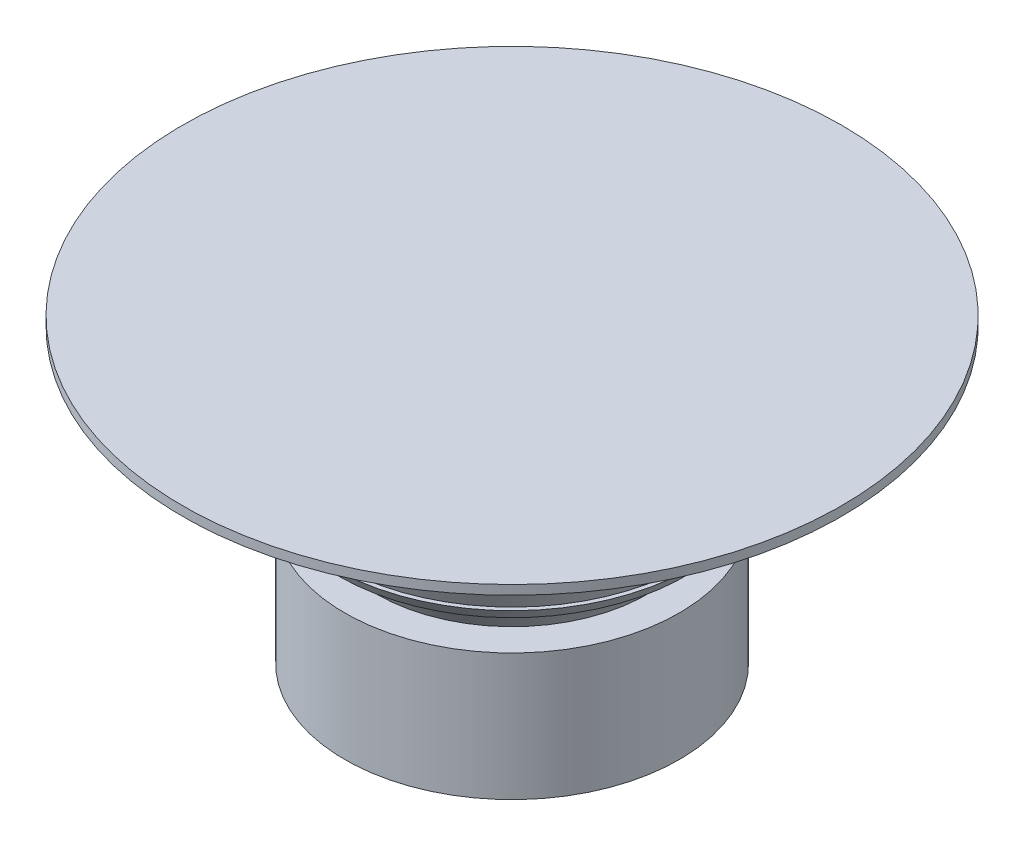
SolidWorks part; units mm, degrees
ref_plane "Front Plane" through (0, 0, 0) normal (0, 0, 1) x (1, 0, 0)
ref_plane "Top Plane" through (0, 0, 0) normal (0, 1, 0) x (1, 0, 0)
ref_plane "Right Plane" through (0, 0, 0) normal (1, 0, 0) x (0, 0, -1)
sketch "Sketch1" plane through (0, 0, 0) normal (0, 0, 1) x (1, 0, 0)
  line L0 (0, 123.363) -> (-135.2932, 123.363)
  line L1 (-135.2932, 119.5555) -> (-113.7173, 119.5555)
  line L2 (-113.7173, 119.5555) -> (-113.7173, 111.9405)
  line L3 (0, 109.9098) -> (-45.4362, 109.9098)
  line L4 (0, 70.8195) -> (-17.0068, 70.8195)
  line L5 (-17.5145, 66.2505) -> (-40.8672, 66.2505)
  line L6 (-71.8348, 67.2658) -> (-74.1193, 70.8195)
  line L7 (-64.7275, 66.2505) -> (-70.058, 66.2505)
  line L8 (-55.5895, 52.0358) -> (-63.2045, 65.2352)
  line L9 (0, 119.5555) -> (-113.7173, 119.5555)
  line L10 (-82.242, 97.472) -> (-72.0887, 70.8195)
  line L11 (-80.2113, 92.3953) -> (-81.7343, 95.949)
  line L12 (-81.7343, 95.949) -> (-83.2573, 99.5027)
  line L13 (-83.2573, 99.5027) -> (-84.7803, 103.0563)
  line L14 (-84.7803, 103.0563) -> (-86.5572, 106.61)
  line L15 (-86.5572, 106.61) -> (-88.334, 109.9098)
  line L16 (-61.4277, 109.9098) -> (-45.4362, 109.9098)
  line L17 (-45.4362, 109.9098) -> (-46.4515, 109.656)
  line L18 (-46.4515, 109.656) -> (-47.7207, 109.4022)
  line L19 (-47.7207, 109.4022) -> (-48.736, 109.1483)
  line L20 (-48.736, 109.1483) -> (-49.4975, 108.3868)
  line L21 (-49.4975, 108.3868) -> (-50.5128, 107.6253)
  line L22 (-50.5128, 107.6253) -> (-51.2743, 106.8638)
  line L23 (-51.2743, 106.8638) -> (-51.782, 105.8485)
  line L24 (-51.782, 105.8485) -> (-52.0358, 104.8332)
  line L25 (-52.0358, 104.8332) -> (-52.2897, 103.564)
  line L26 (-52.2897, 103.564) -> (-52.2897, 102.5487)
  line L27 (-52.2897, 102.5487) -> (-52.2897, 101.2795)
  line L28 (-52.2897, 101.2795) -> (-52.0358, 100.2642)
  line L29 (-52.0358, 100.2642) -> (-51.5282, 99.2488)
  line L30 (-51.5282, 99.2488) -> (-50.7667, 98.2335)
  line L31 (-50.7667, 98.2335) -> (-48.9898, 96.4567)
  line L32 (-48.9898, 96.4567) -> (-47.213, 94.6798)
  line L33 (-47.213, 94.6798) -> (-45.4362, 93.1568)
  line L34 (-45.4362, 93.1568) -> (-43.4055, 91.38)
  line L35 (-43.4055, 91.38) -> (-41.3748, 90.1108)
  line L36 (-41.3748, 90.1108) -> (-17.0068, 70.8195)
  line L37 (-40.3595, 66.2505) -> (-63.2045, 106.8638)
  line L38 (-46.9592, 69.8042) -> (-70.5657, 109.9098)
  line L39 (-74.1193, 70.8195) -> (-72.0887, 70.8195)
  line L40 (-46.9592, 69.8042) -> (-46.4515, 68.7888)
  line L41 (-46.4515, 68.7888) -> (-45.69, 68.0273)
  line L42 (-45.69, 68.0273) -> (-44.9285, 67.5197)
  line L43 (-44.9285, 67.5197) -> (-43.9132, 67.012)
  line L44 (-43.9132, 67.012) -> (-42.8978, 66.5043)
  line L45 (-42.8978, 66.5043) -> (-41.8825, 66.5043)
  line L46 (-41.8825, 66.5043) -> (-40.8672, 66.2505)
  line L47 (-55.0818, 66.2505) -> (-40.3595, 66.2505)
  line L48 (-61.1738, 69.8042) -> (-85.288, 109.9098)
  line L49 (-61.1738, 69.8042) -> (-60.4123, 68.7888)
  line L50 (-60.4123, 68.7888) -> (-59.9047, 68.0273)
  line L51 (-59.9047, 68.0273) -> (-58.8893, 67.5197)
  line L52 (-58.8893, 67.5197) -> (-58.1278, 67.012)
  line L53 (-58.1278, 67.012) -> (-57.1125, 66.5043)
  line L54 (-57.1125, 66.5043) -> (-56.0972, 66.5043)
  line L55 (-56.0972, 66.5043) -> (-55.0818, 66.2505)
  line L56 (-63.7122, 66.2505) -> (-55.0818, 66.2505)
  line L57 (-111.6867, 109.9098) -> (-61.4277, 109.9098)
  line L58 (-61.4277, 109.9098) -> (-62.1892, 109.656)
  line L59 (-62.1892, 109.656) -> (-62.443, 109.656)
  line L60 (-62.443, 109.656) -> (-62.9507, 109.1483)
  line L61 (-62.9507, 109.1483) -> (-63.2045, 108.8945)
  line L62 (-63.2045, 108.8945) -> (-63.4583, 108.3868)
  line L63 (-63.4583, 108.3868) -> (-63.4583, 107.8792)
  line L64 (-63.4583, 107.8792) -> (-63.4583, 107.3715)
  line L65 (-63.4583, 107.3715) -> (-63.2045, 106.8638)
  line L66 (-63.2045, 65.2352) -> (-63.4583, 65.7428)
  line L67 (-63.4583, 65.7428) -> (-63.7122, 65.9967)
  line L68 (-63.7122, 65.9967) -> (-64.2198, 66.2505)
  line L69 (-64.2198, 66.2505) -> (-64.7275, 66.2505)
  line L70 (-71.8348, 67.2658) -> (-71.3272, 66.7582)
  line L71 (-71.3272, 66.7582) -> (-71.0733, 66.5043)
  line L72 (-71.0733, 66.5043) -> (-70.5657, 66.2505)
  line L73 (-70.5657, 66.2505) -> (-70.058, 66.2505)
  line L74 (-113.7173, 111.9405) -> (-113.7173, 111.179)
  line L75 (-113.7173, 111.179) -> (-113.4635, 110.9252)
  line L76 (-113.4635, 110.9252) -> (-113.2097, 110.4175)
  line L77 (-113.2097, 110.4175) -> (-112.702, 110.1637)
  line L78 (-112.702, 110.1637) -> (-112.1943, 109.9098)
  line L79 (-112.1943, 109.9098) -> (-111.6867, 109.9098)
  line L80 (0, 123.363) -> (135.0393, 123.363)
  line L81 (135.0393, 119.5555) -> (113.4635, 119.5555)
  line L82 (113.4635, 119.5555) -> (113.4635, 111.9405)
  line L83 (0, 109.9098) -> (45.1823, 109.9098)
  line L84 (0, 70.8195) -> (16.753, 70.8195)
  line L85 (17.2607, 66.2505) -> (40.6133, 66.2505)
  line L86 (71.581, 67.2658) -> (73.8655, 70.8195)
  line L87 (64.4737, 66.2505) -> (69.8042, 66.2505)
  line L88 (55.3357, 52.0358) -> (62.9507, 65.2352)
  line L89 (0, 119.5555) -> (113.4635, 119.5555)
  line L90 (81.9882, 97.472) -> (72.0887, 70.8195)
  line L91 (88.334, 109.9098) -> (86.3033, 106.61)
  line L92 (86.3033, 106.61) -> (84.5265, 103.0563)
  line L93 (84.5265, 103.0563) -> (83.0035, 99.5027)
  line L94 (83.0035, 99.5027) -> (81.4805, 95.949)
  line L95 (81.4805, 95.949) -> (80.2113, 92.3953)
  line L96 (41.121, 90.1108) -> (16.753, 70.8195)
  line L97 (41.121, 90.1108) -> (43.1517, 91.38)
  line L98 (43.1517, 91.38) -> (45.1823, 93.1568)
  line L99 (45.1823, 93.1568) -> (47.213, 94.6798)
  line L100 (47.213, 94.6798) -> (48.736, 96.4567)
  line L101 (48.736, 96.4567) -> (50.5128, 98.2335)
  line L102 (50.5128, 98.2335) -> (51.2743, 99.2488)
  line L103 (51.2743, 99.2488) -> (51.782, 100.2642)
  line L104 (51.782, 100.2642) -> (52.0358, 101.2795)
  line L105 (52.0358, 101.2795) -> (52.2897, 102.5487)
  line L106 (52.2897, 102.5487) -> (52.0358, 103.564)
  line L107 (52.0358, 103.564) -> (52.0358, 104.8332)
  line L108 (52.0358, 104.8332) -> (51.5282, 105.8485)
  line L109 (51.5282, 105.8485) -> (51.0205, 106.8638)
  line L110 (51.0205, 106.8638) -> (50.259, 107.6253)
  line L111 (50.259, 107.6253) -> (49.4975, 108.3868)
  line L112 (49.4975, 108.3868) -> (48.4822, 109.1483)
  line L113 (48.4822, 109.1483) -> (47.4668, 109.4022)
  line L114 (47.4668, 109.4022) -> (46.4515, 109.656)
  line L115 (46.4515, 109.656) -> (45.1823, 109.9098)
  line L116 (61.4277, 109.9098) -> (45.1823, 109.9098)
  line L117 (40.1057, 66.2505) -> (62.9507, 106.8638)
  line L118 (46.7053, 69.8042) -> (70.3118, 109.9098)
  line L119 (73.8655, 70.8195) -> (72.0887, 70.8195)
  line L120 (40.6133, 66.2505) -> (41.6287, 66.5043)
  line L121 (41.6287, 66.5043) -> (42.644, 66.5043)
  line L122 (42.644, 66.5043) -> (43.6593, 67.012)
  line L123 (43.6593, 67.012) -> (44.6747, 67.5197)
  line L124 (44.6747, 67.5197) -> (45.4362, 68.0273)
  line L125 (45.4362, 68.0273) -> (46.1977, 68.7888)
  line L126 (46.1977, 68.7888) -> (46.7053, 69.8042)
  line L127 (54.828, 66.2505) -> (40.1057, 66.2505)
  line L128 (63.4583, 66.2505) -> (54.828, 66.2505)
  line L129 (54.828, 66.2505) -> (55.8433, 66.5043)
  line L130 (55.8433, 66.5043) -> (56.8587, 66.5043)
  line L131 (56.8587, 66.5043) -> (57.874, 67.012)
  line L132 (57.874, 67.012) -> (58.8893, 67.5197)
  line L133 (58.8893, 67.5197) -> (59.6508, 68.0273)
  line L134 (59.6508, 68.0273) -> (60.1585, 68.7888)
  line L135 (60.1585, 68.7888) -> (60.92, 69.8042)
  line L136 (60.92, 69.8042) -> (85.288, 109.9098)
  line L137 (62.9507, 106.8638) -> (63.2045, 107.3715)
  line L138 (63.2045, 107.3715) -> (63.2045, 107.8792)
  line L139 (63.2045, 107.8792) -> (63.2045, 108.3868)
  line L140 (63.2045, 108.3868) -> (62.9507, 108.8945)
  line L141 (62.9507, 108.8945) -> (62.6968, 109.1483)
  line L142 (62.6968, 109.1483) -> (62.443, 109.656)
  line L143 (62.443, 109.656) -> (61.9353, 109.656)
  line L144 (61.9353, 109.656) -> (61.4277, 109.9098)
  line L145 (111.4328, 109.9098) -> (61.4277, 109.9098)
  line L146 (64.4737, 66.2505) -> (63.966, 66.2505)
  line L147 (63.966, 66.2505) -> (63.7122, 65.9967)
  line L148 (63.7122, 65.9967) -> (63.2045, 65.7428)
  line L149 (63.2045, 65.7428) -> (62.9507, 65.2352)
  line L150 (69.8042, 66.2505) -> (70.3118, 66.2505)
  line L151 (70.3118, 66.2505) -> (70.8195, 66.5043)
  line L152 (70.8195, 66.5043) -> (71.3272, 66.7582)
  line L153 (71.3272, 66.7582) -> (71.581, 67.2658)
  line L154 (111.4328, 109.9098) -> (111.9405, 109.9098)
  line L155 (111.9405, 109.9098) -> (112.4482, 110.1637)
  line L156 (112.4482, 110.1637) -> (112.9558, 110.4175)
  line L157 (112.9558, 110.4175) -> (113.2097, 110.9252)
  line L158 (113.2097, 110.9252) -> (113.4635, 111.179)
  line L159 (113.4635, 111.179) -> (113.4635, 111.9405)
  line L160 (135.0393, 119.5555) -> (135.0393, 123.363)
  line L161 (-135.2932, 119.5555) -> (-135.2932, 123.363)
  line L162 (14.4685, 70.8195) -> (-14.7223, 70.8195)
  line L163 (-14.7223, 70.8195) -> (-14.7223, 69.2965)
  line L164 (-14.7223, 69.2965) -> (14.4685, 69.2965)
  line L165 (14.4685, 69.2965) -> (14.4685, 70.8195)
  line L166 (-12.184, 67.7735) -> (-12.9455, 67.7735)
  line L167 (-12.9455, 67.7735) -> (-12.184, 67.7735)
  line L168 (-12.184, 64.4737) -> (-12.184, 67.7735)
  line L169 (-7.1073, 67.7735) -> (-7.1073, 64.4737)
  line L170 (-8.1227, 63.7122) -> (-11.1687, 63.7122)
  line L171 (-12.9455, 69.2965) -> (-12.9455, 67.7735)
  line L172 (-7.1073, 67.7735) -> (-6.3458, 67.7735)
  line L173 (-6.3458, 67.7735) -> (-6.3458, 69.2965)
  line L174 (-12.184, 67.7735) -> (-12.9455, 67.7735)
  line L175 (-6.3458, 67.7735) -> (-7.1073, 67.7735)
  line L176 (-12.184, 64.4737) -> (-11.1687, 63.7122)
  line L177 (-7.1073, 64.4737) -> (-8.1227, 63.7122)
  line L178 (-8.1227, 63.966) -> (-11.1687, 63.966)
  line L179 (-10.661, 66.7582) -> (-10.661, 66.2505)
  line L180 (-8.8842, 66.2505) -> (-8.8842, 66.7582)
  line L181 (-10.661, 66.2505) -> (-10.4072, 65.9967)
  line L182 (-10.4072, 65.9967) -> (-10.4072, 65.7428)
  line L183 (-10.4072, 65.7428) -> (-9.8995, 65.489)
  line L184 (-9.8995, 65.489) -> (-9.6457, 65.2352)
  line L185 (-9.6457, 65.2352) -> (-9.3918, 65.489)
  line L186 (-9.3918, 65.489) -> (-9.138, 65.7428)
  line L187 (-9.138, 65.7428) -> (-8.8842, 65.9967)
  line L188 (-8.8842, 65.9967) -> (-8.8842, 66.2505)
  line L189 (-8.8842, 66.7582) -> (-8.8842, 67.012)
  line L190 (-8.8842, 67.012) -> (-9.138, 67.2658)
  line L191 (-9.138, 67.2658) -> (-9.3918, 67.5197)
  line L192 (-9.3918, 67.5197) -> (-9.6457, 67.5197)
  line L193 (-9.6457, 67.5197) -> (-9.8995, 67.5197)
  line L194 (-9.8995, 67.5197) -> (-10.4072, 67.2658)
  line L195 (-10.4072, 67.2658) -> (-10.4072, 67.012)
  line L196 (-10.4072, 67.012) -> (-10.661, 66.7582)
  line L197 (-8.8842, 66.5043) -> (-8.8842, 66.7582)
  line L198 (-8.8842, 66.7582) -> (-9.138, 67.012)
  line L199 (-9.138, 67.012) -> (-9.3918, 67.2658)
  line L200 (-9.3918, 67.2658) -> (-9.6457, 67.2658)
  line L201 (-9.6457, 67.2658) -> (-9.8995, 67.2658)
  line L202 (-9.8995, 67.2658) -> (-10.4072, 67.012)
  line L203 (-10.4072, 67.012) -> (-10.4072, 66.7582)
  line L204 (-10.4072, 66.7582) -> (-10.661, 66.5043)
  line L205 (-12.184, 64.7275) -> (-11.1687, 63.966)
  line L206 (-7.1073, 64.7275) -> (-8.1227, 63.966)
  line L207 (-18.5298, 64.4737) -> (-14.4685, 68.7888)
  line L208 (-14.4685, 68.7888) -> (-12.9455, 68.7888)
  line L209 (-12.9455, 68.7888) -> (-12.9455, 69.2965)
  line L210 (-19.5452, 64.2198) -> (-14.7223, 69.2965)
  line L211 (-15.7377, 68.2812) -> (-15.23, 67.7735)
  line L212 (-19.2913, 63.966) -> (-19.5452, 64.2198)
  line L213 (-19.2913, 63.966) -> (-18.5298, 64.4737)
  line L214 (-18.5298, 64.4737) -> (-19.0375, 64.9813)
  line L215 (-2.2845, 68.2812) -> (0, 68.2812)
  line L216 (2.0307, 68.2812) -> (0, 68.2812)
  line L217 (-3.2998, 69.2965) -> (-3.2998, 68.7888)
  line L218 (-3.2998, 68.7888) -> (-3.046, 68.535)
  line L219 (-3.046, 68.535) -> (-2.7922, 68.2812)
  line L220 (-2.7922, 68.2812) -> (-2.2845, 68.2812)
  line L221 (2.0307, 68.2812) -> (2.5383, 68.2812)
  line L222 (2.5383, 68.2812) -> (2.7922, 68.535)
  line L223 (2.7922, 68.535) -> (3.046, 68.7888)
  line L224 (3.046, 68.7888) -> (3.046, 69.2965)
  line L225 (6.3458, 69.2965) -> (6.092, 69.2965)
  line L226 (12.184, 67.7735) -> (12.6917, 67.7735)
  line L227 (12.6917, 67.7735) -> (12.184, 67.7735)
  line L228 (12.184, 64.4737) -> (12.184, 67.7735)
  line L229 (6.8535, 67.7735) -> (6.8535, 64.4737)
  line L230 (7.8688, 63.7122) -> (10.9148, 63.7122)
  line L231 (12.6917, 69.2965) -> (12.6917, 67.7735)
  line L232 (6.8535, 67.7735) -> (6.092, 67.7735)
  line L233 (6.092, 67.7735) -> (6.092, 69.2965)
  line L234 (12.184, 67.7735) -> (12.6917, 67.7735)
  line L235 (6.092, 67.7735) -> (6.8535, 67.7735)
  line L236 (12.184, 64.4737) -> (10.9148, 63.7122)
  line L237 (6.8535, 64.4737) -> (7.8688, 63.7122)
  line L238 (7.8688, 63.966) -> (10.9148, 63.966)
  line L239 (10.4072, 66.7582) -> (10.4072, 66.2505)
  line L240 (8.6303, 66.2505) -> (8.6303, 66.7582)
  line L241 (8.6303, 66.2505) -> (8.6303, 65.9967)
  line L242 (8.6303, 65.9967) -> (8.8842, 65.7428)
  line L243 (8.8842, 65.7428) -> (9.138, 65.489)
  line L244 (9.138, 65.489) -> (9.3918, 65.2352)
  line L245 (9.3918, 65.2352) -> (9.8995, 65.489)
  line L246 (9.8995, 65.489) -> (10.1533, 65.7428)
  line L247 (10.1533, 65.7428) -> (10.1533, 65.9967)
  line L248 (10.1533, 65.9967) -> (10.4072, 66.2505)
  line L249 (10.4072, 66.7582) -> (10.1533, 67.012)
  line L250 (10.1533, 67.012) -> (10.1533, 67.2658)
  line L251 (10.1533, 67.2658) -> (9.8995, 67.5197)
  line L252 (9.8995, 67.5197) -> (9.3918, 67.5197)
  line L253 (9.3918, 67.5197) -> (9.138, 67.5197)
  line L254 (9.138, 67.5197) -> (8.8842, 67.2658)
  line L255 (8.8842, 67.2658) -> (8.6303, 67.012)
  line L256 (8.6303, 67.012) -> (8.6303, 66.7582)
  line L257 (10.4072, 66.5043) -> (10.1533, 66.7582)
  line L258 (10.1533, 66.7582) -> (10.1533, 67.012)
  line L259 (10.1533, 67.012) -> (9.8995, 67.2658)
  line L260 (9.8995, 67.2658) -> (9.3918, 67.2658)
  line L261 (9.3918, 67.2658) -> (9.138, 67.2658)
  line L262 (9.138, 67.2658) -> (8.8842, 67.012)
  line L263 (8.8842, 67.012) -> (8.6303, 66.7582)
  line L264 (8.6303, 66.7582) -> (8.6303, 66.5043)
  line L265 (12.184, 64.7275) -> (10.9148, 63.966)
  line L266 (6.8535, 64.7275) -> (7.8688, 63.966)
  line L267 (18.276, 64.4737) -> (14.2147, 68.7888)
  line L268 (14.2147, 68.7888) -> (12.6917, 68.7888)
  line L269 (12.6917, 68.7888) -> (12.6917, 69.2965)
  line L270 (19.5452, 64.2198) -> (14.4685, 69.2965)
  line L271 (15.4838, 68.2812) -> (14.9762, 67.7735)
  line L272 (19.2913, 63.966) -> (19.5452, 64.2198)
  line L273 (19.2913, 63.966) -> (18.276, 64.4737)
  line L274 (18.276, 64.4737) -> (18.7837, 64.9813)
  line L275 (68.535, 6.8535) -> (68.535, 52.0358)
  line L276 (68.535, 52.0358) -> (0, 52.0358)
  line L277 (24.8757, 0) -> (61.6815, 0)
  line L278 (67.5197, 52.0358) -> (68.535, 52.0358)
  line L279 (61.6815, 0) -> (62.6968, 0)
  line L280 (62.6968, 0) -> (63.7122, 0.2538)
  line L281 (63.7122, 0.2538) -> (64.7275, 0.7615)
  line L282 (64.7275, 0.7615) -> (65.7428, 1.2692)
  line L283 (65.7428, 1.2692) -> (66.5043, 2.0307)
  line L284 (66.5043, 2.0307) -> (67.2658, 2.7922)
  line L285 (67.2658, 2.7922) -> (67.7735, 3.8075)
  line L286 (67.7735, 3.8075) -> (68.2812, 4.8228)
  line L287 (68.2812, 4.8228) -> (68.535, 5.8382)
  line L288 (68.535, 5.8382) -> (68.535, 6.8535)
  line L289 (-68.7888, 6.8535) -> (-68.7888, 52.0358)
  line L290 (-68.7888, 52.0358) -> (0, 52.0358)
  line L291 (-25.1295, 0) -> (-61.9353, 0)
  line L292 (-67.7735, 52.0358) -> (-68.7888, 52.0358)
  line L293 (-68.7888, 6.8535) -> (-68.7888, 5.8382)
  line L294 (-68.7888, 5.8382) -> (-68.535, 4.8228)
  line L295 (-68.535, 4.8228) -> (-68.0273, 3.8075)
  line L296 (-68.0273, 3.8075) -> (-67.5197, 2.7922)
  line L297 (-67.5197, 2.7922) -> (-66.7582, 2.0307)
  line L298 (-66.7582, 2.0307) -> (-65.9967, 1.2692)
  line L299 (-65.9967, 1.2692) -> (-64.9813, 0.7615)
  line L300 (-64.9813, 0.7615) -> (-63.966, 0.2538)
  line L301 (-63.966, 0.2538) -> (-62.9507, 0)
  line L302 (-62.9507, 0) -> (-61.9353, 0)
  line L303 (-8.8842, 66.2505) -> (-10.661, 66.2505)
  line L304 (0, 66.2505) -> (-7.1073, 66.2505)
  line L305 (8.6303, 66.2505) -> (10.4072, 66.2505)
  line L306 (0, 66.2505) -> (6.8535, 66.2505)
  line L307 (12.184, 66.2505) -> (16.4992, 66.2505)
  line L308 (-12.184, 66.2505) -> (-16.753, 66.2505)
  line L309 (-108.133, 130.4703) -> (0, 130.4703)
  line L310 (-108.133, 130.4703) -> (-109.4022, 130.4703)
  line L311 (-109.4022, 130.4703) -> (-110.4175, 130.2165)
  line L312 (-110.4175, 130.2165) -> (-111.4328, 129.7088)
  line L313 (-111.4328, 129.7088) -> (-112.1943, 129.2012)
  line L314 (-112.1943, 129.2012) -> (-113.2097, 128.4397)
  line L315 (-113.2097, 128.4397) -> (-113.9712, 127.6782)
  line L316 (-113.9712, 127.6782) -> (-114.4788, 126.6628)
  line L317 (-114.4788, 126.6628) -> (-114.7327, 125.6475)
  line L318 (-114.7327, 125.6475) -> (-114.9865, 124.6322)
  line L319 (-114.9865, 124.6322) -> (-115.2403, 123.363)
  line L320 (107.8792, 130.4703) -> (0, 130.4703)
  line L321 (114.9865, 123.363) -> (114.9865, 124.6322)
  line L322 (114.9865, 124.6322) -> (114.7327, 125.6475)
  line L323 (114.7327, 125.6475) -> (114.225, 126.6628)
  line L324 (114.225, 126.6628) -> (113.7173, 127.6782)
  line L325 (113.7173, 127.6782) -> (112.9558, 128.4397)
  line L326 (112.9558, 128.4397) -> (112.1943, 129.2012)
  line L327 (112.1943, 129.2012) -> (111.179, 129.7088)
  line L328 (111.179, 129.7088) -> (110.1637, 130.2165)
  line L329 (110.1637, 130.2165) -> (109.1483, 130.4703)
  line L330 (109.1483, 130.4703) -> (107.8792, 130.4703)
  line L331 (-25.1295, 0) -> (24.8757, 0)
  line L332 (0, 28.6832) -> (0, -9.3918)
  line L333 (0, -9.3918) -> (0, 0)
  line L334 (0, 41.3748) -> (0, 35.029)
  line L335 (0, 86.3033) -> (0, 47.7207)
  line L336 (0, 99.2488) -> (0, 92.6492)
  line L337 (0, 143.4158) -> (0, 105.5947)
sketch "Sketch2" plane through (0, 0, 0) normal (0, 0, 1) x (1, 0, 0)
  line L0 (24.8757, 0) -> (61.6815, 0) construction
  line L1 (68.535, 6.8535) -> (68.535, 52.0358) construction
  line L2 (68.535, 52.0358) -> (0, 52.0358) construction
  line L3 (24.8757, 0) -> (68.535, 0)
  line L4 (68.535, 0) -> (68.535, 52.0358)
  line L5 (68.535, 52.0358) -> (55.3357, 52.0358)
  line L6 (17.2607, 66.2505) -> (40.6133, 66.2505) construction
  line L7 (55.3357, 52.0358) -> (62.9507, 65.2352) construction
  line L8 (0, 66.2505) -> (63.5364, 66.2505)
  line L9 (55.3357, 52.0358) -> (63.5364, 66.2505)
  line L10 (0, 0) -> (0, 234.0444) construction
  line L11 (0, -84.0442) -> (0, 84.0442) construction
  line L12 (0, 0) -> (0, 66.2505)
  line L13 (24.8757, 0) -> (0, 0)
revolve "Revolve1" add sketch "Sketch2" angle 360 about L10
sketch "Sketch3" plane through (0, 0, 0) normal (0, 0, 1) x (1, 0, 0)
  line L0 (81.9882, 97.472) -> (72.0887, 70.8195) construction
  line L1 (80.9291, 94.6206) -> (72.0887, 70.8195)
  line L4 (84.5265, 103.0563) -> (83.0035, 99.5027) construction
  line L6 (0, 0) -> (0, 307.7937) construction
  line L7 (73.8655, 70.8195) -> (72.0887, 70.8195) construction
  line L8 (73.8655, 70.8195) -> (72.0887, 70.8195)
  line L9 (71.581, 67.2658) -> (73.8655, 70.8195) construction
  line L10 (64.4737, 66.2505) -> (69.8042, 66.2505) construction
  line L12 (0, 109.9098) -> (45.1823, 109.9098) construction
  line L13 (70.9283, 66.2505) -> (73.8655, 70.8195)
  line L14 (0, 66.2505) -> (70.9283, 66.2505)
  line L15 (0, 109.9098) -> (0, 66.2505)
  line L16 (0, 109.9098) -> (88.334, 109.9098)
  arc A0 (88.334, 109.9098) -> (80.9291, 94.6206) centre (208.6351, 42.2075) ccw
  dimension "D1" = 138.0433
revolve "Revolve2" add sketch "Sketch3" angle 360 about L6
ref_axis "Axis1" through (0, 250.9805, 0) along (0, -1, 0)
sketch "Sketch5" plane through (0, 0, 0) normal (0, 0, 1) x (1, 0, 0)
  line L0 (0, 109.9098) -> (45.1823, 109.9098) construction
  line L1 (113.4635, 119.5555) -> (113.4635, 111.9405) construction
  line L2 (135.0393, 119.5555) -> (113.4635, 119.5555) construction
  line L3 (135.0393, 119.5555) -> (135.0393, 123.363) construction
  line L4 (0, 123.363) -> (135.0393, 123.363) construction
  line L5 (0, 109.9098) -> (113.4635, 109.9098)
  line L6 (113.4635, 119.5555) -> (113.4635, 109.9098)
  line L7 (135.0393, 119.5555) -> (113.4635, 119.5555)
  line L8 (135.0393, 119.5555) -> (135.0393, 123.363)
  line L9 (0, 123.363) -> (135.0393, 123.363)
  line L10 (0, 123.363) -> (0, 109.9098)
  line L11 (0, 0) -> (0, 238.5818) construction
  line L12 (0, 250.9805) -> (0, -21.7905) construction
  line L13 (0, -136.3855) -> (0, 136.3855) construction
revolve "Revolve3" add sketch "Sketch5" angle 360 about L11
